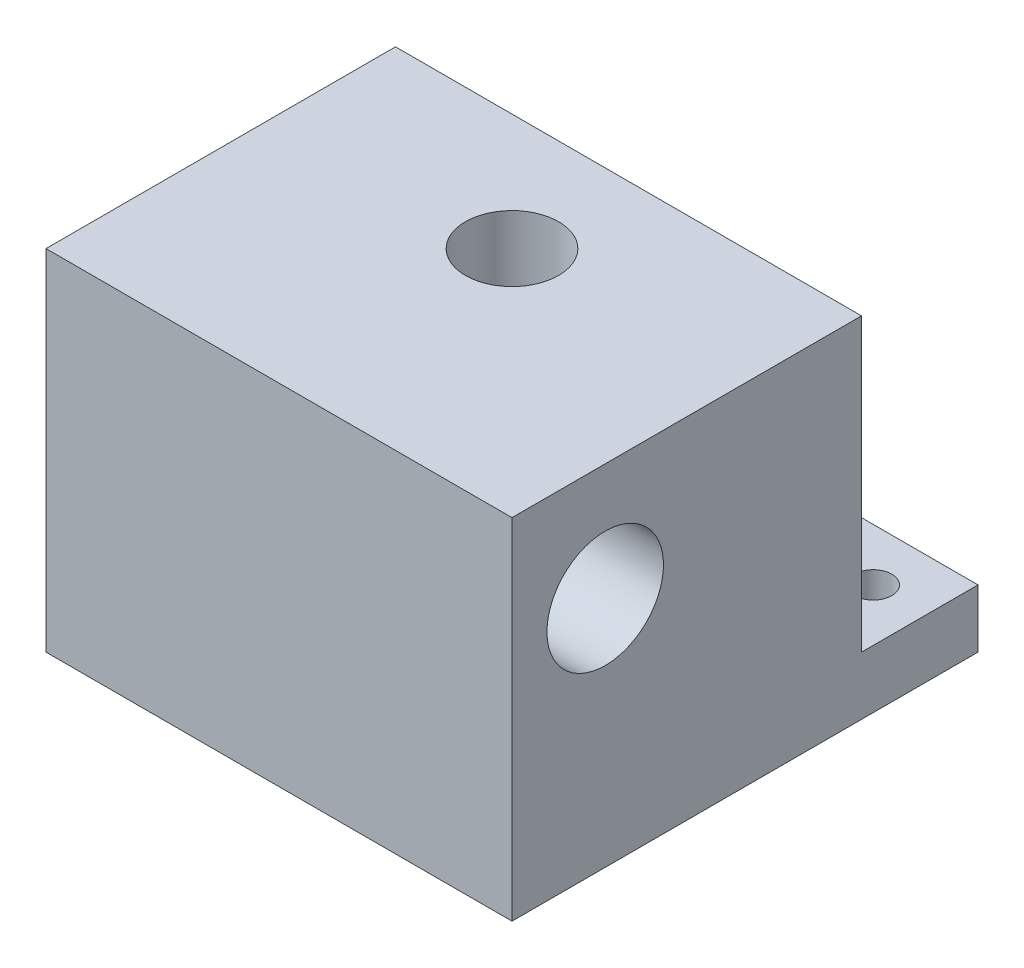
SolidWorks part; units mm, degrees
ref_plane "Front Plane" through (0, 0, 0) normal (0, 0, 1) x (1, 0, 0)
ref_plane "Top Plane" through (0, 0, 0) normal (0, 1, 0) x (1, 0, 0)
ref_plane "Right Plane" through (0, 0, 0) normal (1, 0, 0) x (0, 0, -1)
sketch "Sketch1" plane through (0, 0, 0) normal (0, 1, 0) x (1, 0, 0)
  line L1 (-20, -20) -> (20, -20)
  line L2 (-20, -20) -> (-20, 20)
  line L3 (-20, 20) -> (20, 20)
  line L4 (20, -20) -> (20, 20)
  line L5 (-20, -20) -> (20, 20) construction
  line L6 (-20, 20) -> (20, -20) construction
  point P0 (0, 0)
  dimension "D1" = 40
extrude "Boss-Extrude1" add sketch "Sketch1" along normal blind 30
sketch "Sketch2" plane through (0, 30, 0) normal (0, 1, 0) x (1, 0, 0)
  circle A0 centre (0, 0) radius 4
  dimension "D1" = 8
extrude "Cut-Extrude1" cut sketch "Sketch2" against normal through all
sketch "Sketch3" plane through (-20, 0, 0) normal (-1, 0, 0) x (0, 0, 1)
  line L0 (-20, 0) -> (20, 0) construction
  circle A0 centre (12, 20) radius 5
  dimension "D1" = 10
  dimension "D2" = 20
  dimension "D3" = 12
extrude "Cut-Extrude2" cut sketch "Sketch3" against normal through all both and the other way through all contours A0
sketch "Sketch4" plane through (-20, 0, 0) normal (-1, 0, 0) x (0, 0, 1)
  line L0 (-20, 0) -> (20, 0) construction
  line L1 (-20, 30) -> (-10, 30)
  line L2 (-20, 30) -> (-20, 5)
  line L3 (-20, 5) -> (-10, 5)
  line L4 (-10, 30) -> (-10, 5)
  dimension "D1" = 10
  dimension "D2" = 5
extrude "Cut-Extrude3" cut sketch "Sketch4" against normal through all
hole_wizard "M3 Clearance Hole1" positions "Sketch5" profile "Sketch6" hole size "M3" standard "ISO"
sketch "Sketch5" plane through (0, 5, 0) normal (0, 1, 0) x (1, 0, 0)
  line L0 (-15.5, 15.5) -> (15.5, 15.5) construction
  point P1 (-15.5, 15.5)
  point P2 (15.5, 15.5)
  point P5 (0, 15.5)
  dimension "D1" = 31
  dimension "D2" = 15.5
sketch "Sketch6" plane through (-15.5, 5, -15.5) normal (1, 0, 0) x (0, 0, 1)
  line L0 (0, 0) -> (0, 11.0614)
  line L1 (0, 11.0614) -> (1.6, 10.1)
  line L2 (1.6, 10.1) -> (1.6, 0)
  line L5 (1.6, 0) -> (0, 0)
  line L10 (0, 11.0614) -> (-1.6, 10.1) construction
  line L11 (0, -6.35) -> (0, 107.95) construction
  dimension "Hole Dia." = 3.2
  dimension "Hole Depth" = 10.1
  dimension "Drill Angle" = 118
